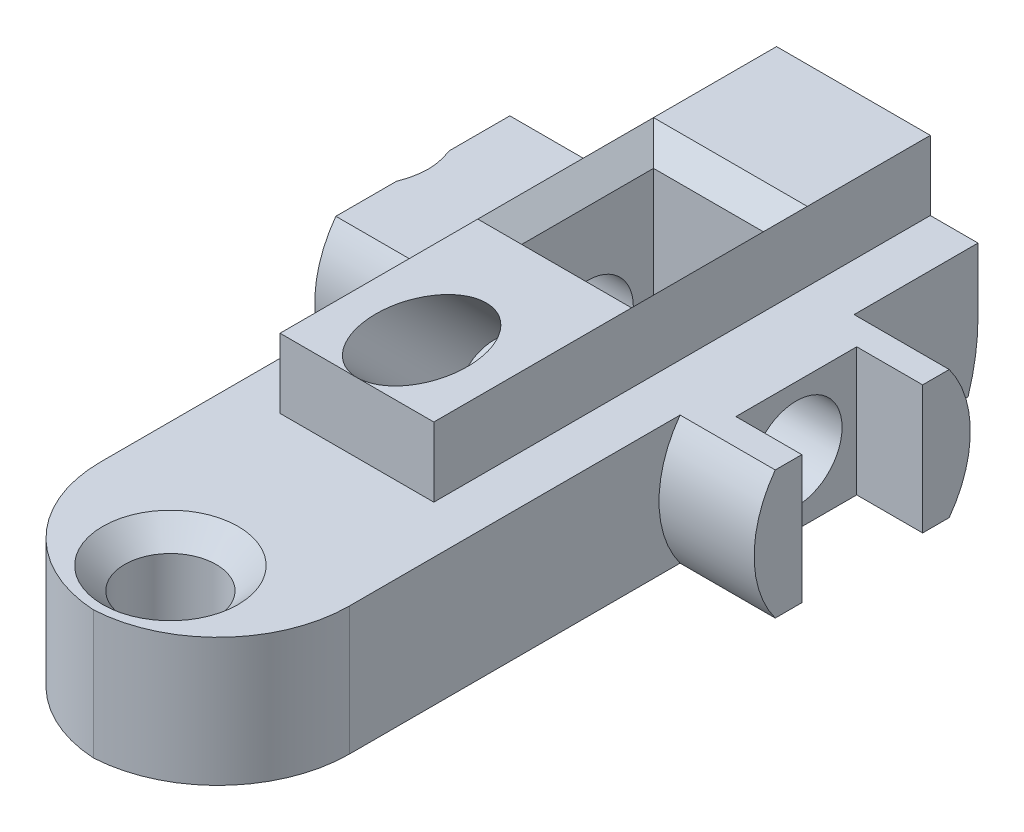
SolidWorks part; units mm, degrees
ref_plane "Front Plane" through (0, 0, 0) normal (0, 0, 1) x (1, 0, 0)
ref_plane "Top Plane" through (0, 0, 0) normal (0, 1, 0) x (1, 0, 0)
ref_plane "Right Plane" through (0, 0, 0) normal (1, 0, 0) x (0, 0, -1)
sketch "Sketch2" plane through (0, 0, 0) normal (1, 0, 0) x (0, 0, -1)
  line L0 (0, 4.92) -> (0, 2.92) construction
  line L1 (0, -4.92) -> (0, -2.92) construction
  line L2 (3.9598, -2.92) -> (-3.9598, -2.92)
  line L3 (3.9598, 2.92) -> (-3.9598, 2.92)
  circle A0 centre (0, 0) radius 4.92 construction
  arc A1 (-3.9598, 2.92) -> (-3.9598, -2.92) centre (0, 0) ccw
  arc A2 (3.9598, 2.92) -> (3.9598, -2.92) centre (0, 0) cw
  point P10 (0, -2.92)
  point P12 (0, 2.92)
  dimension "D1" = 9.84
  dimension "D2" = 2
extrude "Boss-Extrude1" add sketch "Sketch2" along normal blind 20 contours A2 L3 A1 L2 region at (0, 0, 0)
sketch "Sketch3" plane through (0, 0, 0) normal (0, 0, 1) x (1, 0, 0)
  line L0 (10, 2.92) -> (10, -2.92) construction
  line L1 (20, 2.92) -> (0, 2.92) construction
  line L2 (20, -2.92) -> (0, -2.92) construction
  line L4 (4.33, -2.92) -> (15.67, -2.92)
  line L5 (4.33, -2.92) -> (4.33, 2.92)
  line L6 (4.33, 2.92) -> (15.67, 2.92)
  line L7 (15.67, -2.92) -> (15.67, 2.92)
  line L8 (4.33, -2.92) -> (15.67, 2.92) construction
  line L9 (4.33, 2.92) -> (15.67, -2.92) construction
  point P6 (10, 0)
  dimension "D1" = 11.34
extrude "Boss-Extrude2" add sketch "Sketch3" along normal blind 25
fillet "Fillet1" radius 6 2 edges at (15.67, 0, 25) (4.33, 0, 25)
sketch "Sketch4" plane through (0, -2.92, 0) normal (0, -1, 0) x (1, 0, 0)
  line L0 (10, 7) -> (10, -3.9598) construction
  line L1 (20, -3.9598) -> (0, -3.9598) construction
  line L3 (13.5, 4.0402) -> (6.5, 4.0402)
  line L4 (13.5, 4.0402) -> (13.5, -3.9598)
  line L5 (13.5, -3.9598) -> (6.5, -3.9598)
  line L6 (6.5, 4.0402) -> (6.5, -3.9598)
  line L7 (13.5, 4.0402) -> (6.5, -3.9598) construction
  line L8 (13.5, -3.9598) -> (6.5, 4.0402) construction
  point P5 (10, 0.0402)
  dimension "D1" = 7
  dimension "D2" = 8
extrude "Boss-Extrude3" add sketch "Sketch4" against normal blind 9
sketch "Sketch10" plane through (0, 0, 0) normal (0, 0, 1) x (1, 0, 0)
  line L6 (10, -2.92) -> (15.67, -2.92) construction
  line L7 (15.67, -2.92) -> (15.67, 2.92) construction
  line L8 (15.67, 2.92) -> (10, 2.92) construction
  line L9 (4.33, 2.92) -> (4.33, -2.92) construction
  line L10 (4.33, -2.92) -> (10, -2.92) construction
  line L11 (10, 2.92) -> (4.33, 2.92) construction
  line L12 (10, -2.92) -> (15.67, -2.92)
  line L13 (15.67, -2.92) -> (15.67, 2.92)
  line L14 (15.67, 2.92) -> (13.5, 2.92)
  line L15 (4.33, 2.92) -> (4.33, -2.92)
  line L16 (4.33, -2.92) -> (10, -2.92)
  line L17 (6.5, 2.92) -> (4.33, 2.92)
  line L22 (6.5, 2.92) -> (13.5, 2.92)
  line L23 (13.5, 2.92) -> (13.5, 6.08)
  line L24 (13.5, 6.08) -> (6.5, 6.08)
  line L25 (6.5, 6.08) -> (6.5, 2.92)
  line L27 (13.5, 2.92) -> (13.5, 6.08)
  line L28 (13.5, 6.08) -> (6.5, 6.08)
  line L29 (6.5, 6.08) -> (6.5, 2.92)
  dimension "D1" = 0
extrude "Boss-Extrude4" add sketch "Sketch10" against normal blind 9.6 and the other way blind 13
sketch "Sketch5" plane through (0, 6.08, 0) normal (0, 1, 0) x (1, 0, 0)
  line L0 (10, -3.9598) -> (10, 3.9598) construction
  line L4 (7.5, -3) -> (12.5, -3)
  line L5 (7.5, -3) -> (7.5, 3)
  line L6 (7.5, 3) -> (12.5, 3)
  line L7 (12.5, -3) -> (12.5, 3)
  line L8 (7.5, -3) -> (12.5, 3) construction
  line L9 (7.5, 3) -> (12.5, -3) construction
  line L10 (6.5, 3.9598) -> (13.5, 3.9598) construction
  line L11 (6.5, -13) -> (6.5, 9.6) construction
  line L12 (13.5, 9.6) -> (13.5, -13) construction
  line L14 (20, 3.9598) -> (15.67, 3.9598) construction
  line L15 (6.5, -3.9598) -> (13.5, -3.9598) construction
  line L16 (6.5, -13) -> (6.5, 9.6) construction
  line L17 (13.5, 9.6) -> (13.5, -13) construction
  line L18 (4.33, -3.9598) -> (0, -3.9598) construction
  point P4 (9.4714, -3.9153)
  point P6 (10, 0)
  point P12 (10, -3.9598)
  dimension "D1" = 6
  dimension "D2" = 5
extrude "Cut-Extrude1" cut sketch "Sketch5" against normal up to surface (9 mm away) up to face at (10, -2.92, 3.5422)
sketch "Sketch6" plane through (0, 2.92, 0) normal (0, 1, 0) x (1, 0, 0)
  line L0 (10, -21.4909) -> (10, -24.9909) construction
  circle A0 centre (10, -21.4909) radius 2.0825
  arc A1 (4.33, -19) -> (10, -24.9909) centre (10.33, -19) ccw construction
  arc A2 (10, -24.9909) -> (15.67, -19) centre (9.67, -19) ccw construction
  point P3 (10.3319, -7.4908)
  point P4 (10, -12)
  dimension "D1" = 4.165
  dimension "D2" = 3.5
extrude "Cut-Extrude2" cut sketch "Sketch6" against normal up to surface (5.84 mm away) up to face at (10, -2.92, 0)
sketch "Sketch8" plane through (20, 0, 0) normal (1, 0, 0) x (0, 0, -1)
  line L1 (-3, -2.92) -> (3, -2.92) construction
  line L2 (-3, -2.92) -> (3, -2.92) construction
  line L3 (0, -2.92) -> (0, 0.08) construction
  circle A0 centre (0, 0.08) radius 2.0825
  dimension "D2" = 4.165
  dimension "D1" = 3
extrude "Cut-Extrude3" cut sketch "Sketch8" against normal up to surface (20 mm away) up to face at (0, 0, 0)
sketch "Sketch9" plane through (0, 2.92, 0) normal (0, 1, 0) x (1, 0, 0)
  line L0 (20, -2.0825) -> (20, 2.0825) construction
  line L1 (20, -2.0825) -> (20, 2.0825) construction
  line L2 (20, -2.75) -> (20, 2.75)
  line L3 (20, 3.9598) -> (20, -3.9598) construction
  line L4 (20, 2.75) -> (17, 2.75)
  line L5 (17, 2.75) -> (17, -2.75)
  line L6 (17, -2.75) -> (20, -2.75)
  point P7 (20, 0)
  dimension "D1" = 3
  dimension "D2" = 5.5
extrude "Cut-Extrude4" cut sketch "Sketch9" against normal up to surface (5.84 mm away) up to face at (10, -2.92, 19.4084)
chamfer "Chamfer1" distance 1 angle 45 6 edges at (10, 6.08, 3) (7.5, 6.08, 0) (10, 6.08, -3) (12.5, 6.08, 0) (10, 2.92, 23.5734) (0, 0.08, -2.0825)
sketch "Sketch11" plane through (4.33, 0, 0) normal (-1, 0, 0) x (0, 0, 1)
  line L0 (-9.6, 2.92) -> (-9.6, -2.92) construction
  line L1 (-9.6, -2.92) -> (-3.9598, -2.92) construction
  line L2 (-9.1451, -2.92) -> (-9.6, -2.92)
  line L3 (-9.6, -2.92) -> (-9.6, 0)
  arc A0 (-9.6, 0) -> (-9.1451, -2.92) centre (0, 0) ccw
extrude "Cut-Extrude5" cut sketch "Sketch11" against normal up to surface (11.34 mm away) up to face at (15.67, 0, -7.0199)
ref_plane "Plane1" through (0, 9.54, 9.54) normal (0, 0.7071, 0.7071) x (-1, 0, 0)
sketch "Sketch13" plane through (0, 9.54, 9.54) normal (0, 0.7071, 0.7071) x (-1, 0, 0)
  line L0 (-13.5, 4.8932) -> (-6.5, 4.8932) construction
  line L1 (-13.5, 4.8932) -> (-6.5, 4.8932) construction
  line L2 (-10, 4.8932) -> (-10, 2.8107) construction
  circle A0 centre (-10, 2.8107) radius 2.0825
  point P5 (-10, 2.5287)
  dimension "D1" = 4.165
extrude "Cut-Extrude7" cut sketch "Sketch13" against normal blind 8
